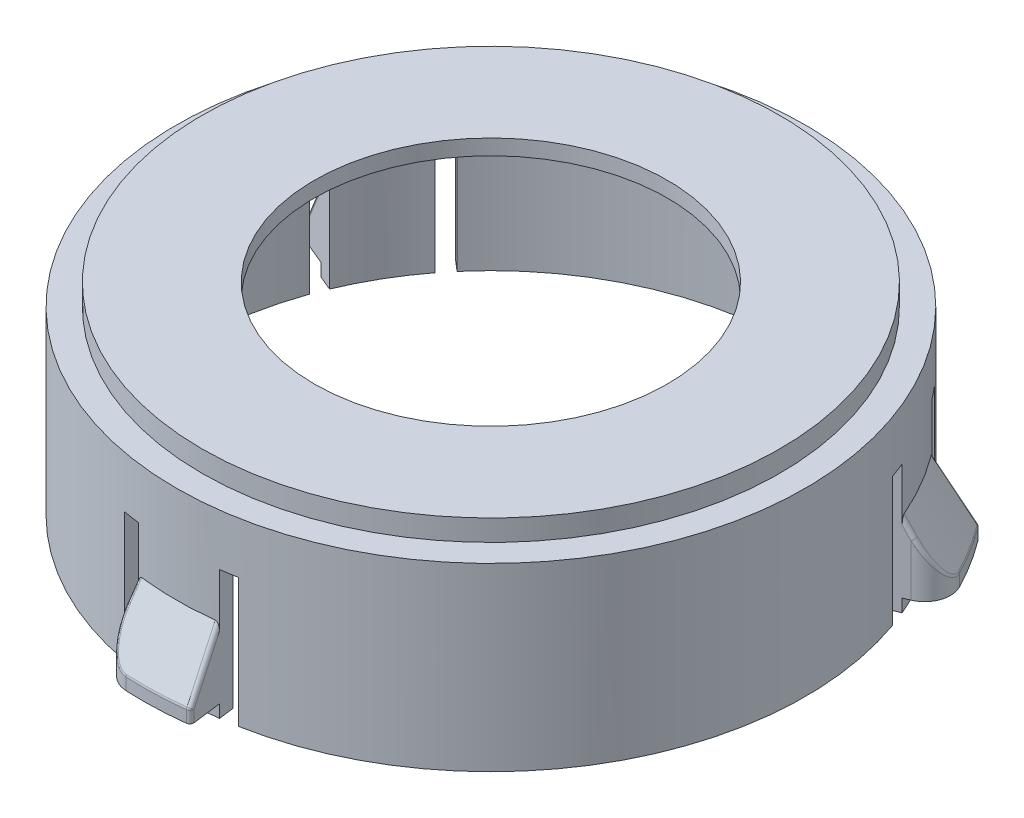
SolidWorks part; units mm, degrees
ref_plane "Front Plane" through (0, 0, 0) normal (0, 0, 1) x (1, 0, 0)
ref_plane "Top Plane" through (0, 0, 0) normal (0, 1, 0) x (1, 0, 0)
ref_plane "Right Plane" through (0, 0, 0) normal (1, 0, 0) x (0, 0, -1)
sketch "Sketch1" plane through (0, 0, 0) normal (0, 1, 0) x (1, 0, 0)
  circle A0 centre (0, 0) radius 24.5
  dimension "D1" = 49
extrude "Boss-Extrude1" add sketch "Sketch1" along normal blind 15.7
sketch "Sketch2" plane through (0, 15.7, 0) normal (0, 1, 0) x (1, 0, 0)
  circle A0 centre (0, 0) radius 22.5
  circle A1 centre (0, 0) radius 24.5 construction
  circle A2 centre (0, 0) radius 24.5
  dimension "D1" = 45
extrude "Cut-Extrude1" cut sketch "Sketch2" against normal blind 1.65
sketch "Sketch3" plane through (0, 15.7, 0) normal (0, 1, 0) x (1, 0, 0)
  circle A0 centre (0, 0) radius 13.75
  dimension "D1" = 27.5
shell "Shell1" thickness 1.2 removed face at (0, 0, 24.5)
extrude "Cut-Extrude2" cut sketch "Sketch3" against normal up to surface (1.2 mm away) up to face at (0, 14.5, 21.3)
sketch "Sketch4" plane through (0, 0, 0) normal (1, 0, 0) x (0, 0, -1)
  line L0 (-24.5, 6.5) -> (-24.5, 1)
  line L1 (-24.5, 14.05) -> (-24.5, 0) construction
  line L2 (-24.5, 14.05) -> (-24.5, 0) construction
  line L3 (-24.5, 1) -> (-27.1, 1)
  line L4 (-27.1, 1) -> (-27.1, 2)
  line L5 (-27.1, 2) -> (-24.5, 6.5)
  dimension "D1" = 2.6
  dimension "D2" = 1
  dimension "D3" = 5.5
  dimension "D4" = 1
ref_plane "Plane1" through (0, 1, 24.5) normal (0, -1, 0) x (-1, 0, 0)
sketch "Sketch5" plane through (0, 1, 24.5) normal (0, -1, 0) x (-1, 0, 0)
  line L0 (0, 0) -> (0, -8.4757) construction
  line L1 (0, 0) -> (0, -2.6) construction
  line L2 (0, -2.6) -> (-6.262, -2.6) construction
  line L3 (-3.5, -2.373) -> (-3.5, -2.6) construction
  line L4 (3.5, -2.373) -> (3.5, -2.6) construction
  circle A2 centre (0, 24.5) radius 27.1
  arc A3 (-3.5, -2.373) -> (3.5, -2.373) centre (0, 24.5) ccw
  point P15 (0, -2.6)
  dimension "D2" = 3.5
  dimension "D3" = 3.5
  dimension "D1" = 2.6
sweep "Sweep1" add profiles "Sketch4" path "Sketch5"
fillet "Fillet2" radius 2 1 edges at (-3.5, 1.5, 26.873)
fillet "Fillet3" radius 0.3 5 edges at (-3.1978, 6.0498, 24.5527) (1.0805, 2, 27.0784) (3.5, 1.5, 26.873) (3.3321, 4.25, 25.5839) (-2.2759, 2.3787, 26.7847)
sketch "Sketch7" plane through (0, 0, 0) normal (0, -1, 0) x (1, 0, 0)
  line L0 (3.461, 26.5739) -> (3.1642, 24.2948) construction
  line L1 (-3.2314, 24.8106) -> (-3.1642, 24.2948) construction
  line L2 (3.461, 26.5739) -> (3.1642, 24.2948) construction
  line L3 (-3.2314, 24.8106) -> (-3.1642, 24.2948) construction
  line L4 (0, 0) -> (7.9298, 43.1191) construction
  line L5 (0, 0) -> (-8.9475, 48.653) construction
  line L6 (-3.1642, 24.2948) -> (-3.0092, 23.1049)
  line L7 (-4.4314, 24.0959) -> (-4.2143, 22.9157)
  line L8 (3.1642, 24.2948) -> (3.0092, 23.1049)
  line L9 (4.4314, 24.0959) -> (4.2143, 22.9157)
  circle A0 centre (0, 0) radius 23.3 construction
  circle A1 centre (0, 0) radius 24.5 construction
  arc A2 (-3.0092, -23.1049) -> (3.0092, -23.1049) centre (0, 0) ccw
  arc A3 (-3.1642, -24.2948) -> (3.1642, -24.2948) centre (0, 0) ccw
  arc A4 (4.4314, 24.0959) -> (3.1642, 24.2948) centre (0, 0) ccw
  arc A5 (4.2143, 22.9157) -> (3.0092, 23.1049) centre (0, 0) ccw
  arc A6 (-3.0092, 23.1049) -> (-4.2143, 22.9157) centre (0, 0) ccw
  arc A7 (-3.1642, 24.2948) -> (-4.4314, 24.0959) centre (0, 0) ccw
  point P18 (4.4314, 24.0959)
  point P19 (4.2143, 22.9157)
  point P20 (-4.2143, 22.9157)
  point P21 (-4.4314, 24.0959)
  circle M5 centre (0, 0) radius 23.3
  circle M6 centre (0, 0) radius 24.5
  dimension "D1" = 3
  dimension "D2" = 3
extrude "Cut-Extrude3" cut sketch "Sketch7" against normal offset from surface (10.05 mm away) 4 contours L7 L6 M6 M5 | L9 L8 M6 M5 region at (-3.7064, 0, 23.6132) region at (3.7064, 0, 23.6132) up to face at (0, 14.05, 22.5)
pattern_circular "CirPattern2" count 3 over 360 about axis through (0, 14.05, 0) along (0, 1, 0) of "Sweep1", "Fillet2", "Fillet3", "Cut-Extrude3"
